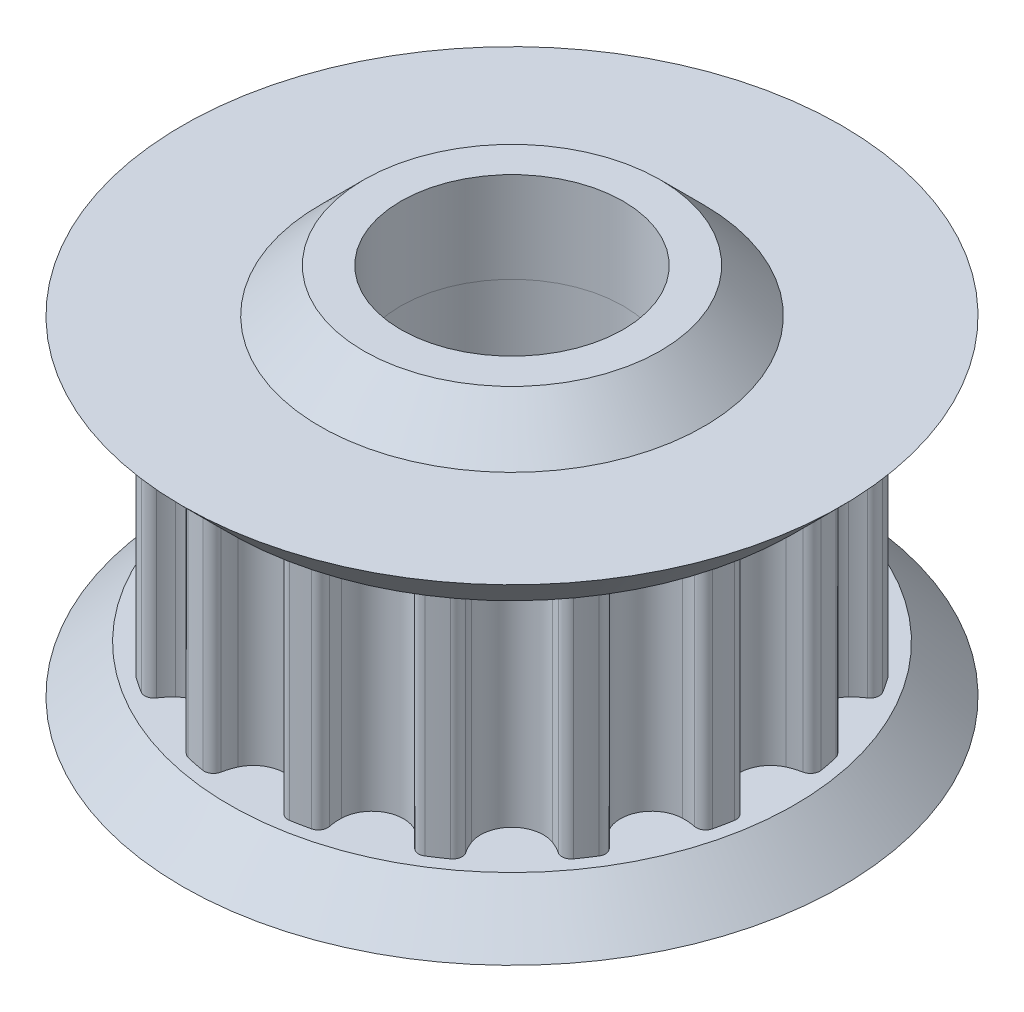
SolidWorks part; units mm, degrees
material "Alum Plate"
ref_plane "Front Plane" through (0, 0, 0) normal (0, 0, 1) x (1, 0, 0)
ref_plane "Top Plane" through (0, 0, 0) normal (0, 1, 0) x (1, 0, 0)
ref_plane "Right Plane" through (0, 0, 0) normal (1, 0, 0) x (0, 0, -1)
other "Bounding Box"
ref_plane "Default Plane" through (-8.9266, -12.7485, 0) normal (-0.1736, 0.9848, 0) x (0.9848, 0.1736, 0)
sketch "Sketch3" plane through (0, 0, 0) normal (0, 0, 1) x (1, 0, 0)
  line L0 (-7.62, 3.175) -> (-8.89, 4.445)
  line L1 (-7.62, 3.175) -> (7.62, 3.175)
  line L2 (-7.62, 3.175) -> (-7.62, -3.175)
  line L3 (-7.62, -3.175) -> (7.62, -3.175)
  line L4 (7.62, 3.175) -> (7.62, -3.175)
  line L5 (-7.62, 3.175) -> (7.62, -3.175) construction
  line L6 (-7.62, -3.175) -> (7.62, 3.175) construction
  line L7 (-8.89, 4.445) -> (-5.176, 4.445)
  line L8 (-5.176, 4.445) -> (-4, 5.621)
  line L9 (-4, 5.621) -> (0, 5.621)
  line L10 (0, 5.621) -> (0, 3.175)
  line L11 (0, -3.175) -> (0, -5.715)
  line L12 (0, -5.715) -> (-4, -5.715)
  line L13 (-4, -5.715) -> (-5.27, -4.445)
  line L14 (-5.27, -4.445) -> (-8.89, -4.445)
  line L15 (-8.89, -4.445) -> (-7.62, -3.175)
  line L16 (0, 11.4717) -> (0, 17.4749) construction
  line L17 (-3, -9.438) -> (-3, 11.1927) construction
  point P0 (0, 0)
  dimension "D1" = 6.35
  dimension "D2" = 15.24
  dimension "D3" = 45
  dimension "D4" = 45
  dimension "D5" = 11.336
  dimension "D6" = 45
  dimension "D7" = 8
  dimension "D8" = 2.54
  dimension "D9" = 1.27
  dimension "D10" = 1.27
  dimension "D11" = 3
sketch "Sketch1" plane through (0, 0, 0) normal (0, 1, 0) x (1, 0, 0)
  line L0 (0, -7.8245) -> (0, 0) construction
  circle A0 centre (0, 0) radius 3
  point P4 (-3, 0)
  point P5 (0, 0)
  arc B0 (-1.8508, -6.777) -> (-1.6633, -7.0715) centre (-1.6061, -6.8282) ccw
  arc B1 (-1.6633, -7.0715) -> (-1.1695, -7.1697) centre (0, 0) ccw
  arc B2 (-1.1695, -7.1697) -> (-0.8836, -6.9694) centre (-1.1292, -6.923) ccw
  arc B3 (-0.7739, -6.6229) -> (-0.8836, -6.9694) centre (0.61, -7.2516) ccw
  arc B4 (0.7739, -6.6229) -> (-0.7739, -6.6229) centre (0, -6.9745) ccw
  arc B5 (0.8836, -6.9694) -> (0.7739, -6.6229) centre (-0.61, -7.2516) ccw
  arc B6 (0.8836, -6.9694) -> (1.1695, -7.1697) centre (1.1292, -6.923) ccw
  arc B7 (1.1695, -7.1697) -> (1.6633, -7.0715) centre (0, 0) ccw
  arc B8 (1.6633, -7.0715) -> (1.8508, -6.777) centre (1.6061, -6.8282) ccw
  arc B9 (1.8195, -6.4149) -> (1.8508, -6.777) centre (3.3386, -6.4662) ccw
  arc B10 (3.2495, -5.8226) -> (1.8195, -6.4149) centre (2.669, -6.4436) ccw
  arc B11 (3.4834, -6.1008) -> (3.2495, -5.8226) centre (2.2115, -6.9331) ccw
  arc B12 (3.4834, -6.1008) -> (3.8242, -6.1764) centre (3.6926, -5.9639) ccw
  arc B13 (3.8242, -6.1764) -> (4.2428, -5.8967) centre (0, 0) ccw
  arc B14 (4.2428, -5.8967) -> (4.3033, -5.5529) centre (4.0968, -5.6938) ccw
  arc B15 (4.1359, -5.2303) -> (4.3033, -5.5529) centre (5.559, -4.6963) ccw
  arc B16 (5.2303, -4.1359) -> (4.1359, -5.2303) centre (4.9317, -4.9317) ccw
  arc B17 (5.5529, -4.3033) -> (5.2303, -4.1359) centre (4.6963, -5.559) ccw
  arc B18 (5.5529, -4.3033) -> (5.8967, -4.2428) centre (5.6938, -4.0968) ccw
  arc B19 (5.8967, -4.2428) -> (6.1764, -3.8242) centre (0, 0) ccw
  arc B20 (6.1764, -3.8242) -> (6.1008, -3.4834) centre (5.9639, -3.6926) ccw
  arc B21 (5.8226, -3.2495) -> (6.1008, -3.4834) centre (6.9331, -2.2115) ccw
  arc B22 (6.4149, -1.8195) -> (5.8226, -3.2495) centre (6.4436, -2.669) ccw
  arc B23 (6.777, -1.8508) -> (6.4149, -1.8195) centre (6.4662, -3.3386) ccw
  arc B24 (6.777, -1.8508) -> (7.0715, -1.6633) centre (6.8282, -1.6061) ccw
  arc B25 (7.0715, -1.6633) -> (7.1697, -1.1695) centre (0, 0) ccw
  arc B26 (7.1697, -1.1695) -> (6.9694, -0.8836) centre (6.923, -1.1292) ccw
  arc B27 (6.6229, -0.7739) -> (6.9694, -0.8836) centre (7.2516, 0.61) ccw
  arc B28 (6.6229, 0.7739) -> (6.6229, -0.7739) centre (6.9745, 0) ccw
  arc B29 (6.9694, 0.8836) -> (6.6229, 0.7739) centre (7.2516, -0.61) ccw
  arc B30 (6.9694, 0.8836) -> (7.1697, 1.1695) centre (6.923, 1.1292) ccw
  arc B31 (7.1697, 1.1695) -> (7.0715, 1.6633) centre (0, 0) ccw
  arc B32 (7.0715, 1.6633) -> (6.777, 1.8508) centre (6.8282, 1.6061) ccw
  arc B33 (6.4149, 1.8195) -> (6.777, 1.8508) centre (6.4662, 3.3386) ccw
  arc B34 (5.8226, 3.2495) -> (6.4149, 1.8195) centre (6.4436, 2.669) ccw
  arc B35 (6.1008, 3.4834) -> (5.8226, 3.2495) centre (6.9331, 2.2115) ccw
  arc B36 (6.1008, 3.4834) -> (6.1764, 3.8242) centre (5.9639, 3.6926) ccw
  arc B37 (6.1764, 3.8242) -> (5.8967, 4.2428) centre (0, 0) ccw
  arc B38 (5.8967, 4.2428) -> (5.5529, 4.3033) centre (5.6938, 4.0968) ccw
  arc B39 (5.2303, 4.1359) -> (5.5529, 4.3033) centre (4.6963, 5.559) ccw
  arc B40 (4.1359, 5.2303) -> (5.2303, 4.1359) centre (4.9317, 4.9317) ccw
  arc B41 (4.3033, 5.5529) -> (4.1359, 5.2303) centre (5.559, 4.6963) ccw
  arc B42 (4.3033, 5.5529) -> (4.2428, 5.8967) centre (4.0968, 5.6938) ccw
  arc B43 (4.2428, 5.8967) -> (3.8242, 6.1764) centre (0, 0) ccw
  arc B44 (3.8242, 6.1764) -> (3.4834, 6.1008) centre (3.6926, 5.9639) ccw
  arc B45 (3.2495, 5.8226) -> (3.4834, 6.1008) centre (2.2115, 6.9331) ccw
  arc B46 (1.8195, 6.4149) -> (3.2495, 5.8226) centre (2.669, 6.4436) ccw
  arc B47 (1.8508, 6.777) -> (1.8195, 6.4149) centre (3.3386, 6.4662) ccw
  arc B48 (1.8508, 6.777) -> (1.6633, 7.0715) centre (1.6061, 6.8282) ccw
  arc B49 (1.6633, 7.0715) -> (1.1695, 7.1697) centre (0, 0) ccw
  arc B50 (1.1695, 7.1697) -> (0.8836, 6.9694) centre (1.1292, 6.923) ccw
  arc B51 (0.7739, 6.6229) -> (0.8836, 6.9694) centre (-0.61, 7.2516) ccw
  arc B52 (-0.7739, 6.6229) -> (0.7739, 6.6229) centre (0, 6.9745) ccw
  arc B53 (-0.8836, 6.9694) -> (-0.7739, 6.6229) centre (0.61, 7.2516) ccw
  arc B54 (-0.8836, 6.9694) -> (-1.1695, 7.1697) centre (-1.1292, 6.923) ccw
  arc B55 (-1.1695, 7.1697) -> (-1.6633, 7.0715) centre (0, 0) ccw
  arc B56 (-1.6633, 7.0715) -> (-1.8508, 6.777) centre (-1.6061, 6.8282) ccw
  arc B57 (-1.8195, 6.4149) -> (-1.8508, 6.777) centre (-3.3386, 6.4662) ccw
  arc B58 (-3.2495, 5.8226) -> (-1.8195, 6.4149) centre (-2.669, 6.4436) ccw
  arc B59 (-3.4834, 6.1008) -> (-3.2495, 5.8226) centre (-2.2115, 6.9331) ccw
  arc B60 (-3.4834, 6.1008) -> (-3.8242, 6.1764) centre (-3.6926, 5.9639) ccw
  arc B61 (-3.8242, 6.1764) -> (-4.2428, 5.8967) centre (0, 0) ccw
  arc B62 (-4.2428, 5.8967) -> (-4.3033, 5.5529) centre (-4.0968, 5.6938) ccw
  arc B63 (-4.1359, 5.2303) -> (-4.3033, 5.5529) centre (-5.559, 4.6963) ccw
  arc B64 (-5.2303, 4.1359) -> (-4.1359, 5.2303) centre (-4.9317, 4.9317) ccw
  arc B65 (-5.5529, 4.3033) -> (-5.2303, 4.1359) centre (-4.6963, 5.559) ccw
  arc B66 (-5.5529, 4.3033) -> (-5.8967, 4.2428) centre (-5.6938, 4.0968) ccw
  arc B67 (-5.8967, 4.2428) -> (-6.1764, 3.8242) centre (0, 0) ccw
  arc B68 (-6.1764, 3.8242) -> (-6.1008, 3.4834) centre (-5.9639, 3.6926) ccw
  arc B69 (-5.8226, 3.2495) -> (-6.1008, 3.4834) centre (-6.9331, 2.2115) ccw
  arc B70 (-6.4149, 1.8195) -> (-5.8226, 3.2495) centre (-6.4436, 2.669) ccw
  arc B71 (-6.777, 1.8508) -> (-6.4149, 1.8195) centre (-6.4662, 3.3386) ccw
  arc B72 (-6.777, 1.8508) -> (-7.0715, 1.6633) centre (-6.8282, 1.6061) ccw
  arc B73 (-7.0715, 1.6633) -> (-7.1697, 1.1695) centre (0, 0) ccw
  arc B74 (-7.1697, 1.1695) -> (-6.9694, 0.8836) centre (-6.923, 1.1292) ccw
  arc B75 (-6.6229, 0.7739) -> (-6.9694, 0.8836) centre (-7.2516, -0.61) ccw
  arc B76 (-6.6229, -0.7739) -> (-6.6229, 0.7739) centre (-6.9745, 0) ccw
  arc B77 (-6.9694, -0.8836) -> (-6.6229, -0.7739) centre (-7.2516, 0.61) ccw
  arc B78 (-6.9694, -0.8836) -> (-7.1697, -1.1695) centre (-6.923, -1.1292) ccw
  arc B79 (-7.1697, -1.1695) -> (-7.0715, -1.6633) centre (0, 0) ccw
  arc B80 (-7.0715, -1.6633) -> (-6.777, -1.8508) centre (-6.8282, -1.6061) ccw
  arc B81 (-6.4149, -1.8195) -> (-6.777, -1.8508) centre (-6.4662, -3.3386) ccw
  arc B82 (-5.8226, -3.2495) -> (-6.4149, -1.8195) centre (-6.4436, -2.669) ccw
  arc B83 (-6.1008, -3.4834) -> (-5.8226, -3.2495) centre (-6.9331, -2.2115) ccw
  arc B84 (-6.1008, -3.4834) -> (-6.1764, -3.8242) centre (-5.9639, -3.6926) ccw
  arc B85 (-6.1764, -3.8242) -> (-5.8967, -4.2428) centre (0, 0) ccw
  arc B86 (-5.8967, -4.2428) -> (-5.5529, -4.3033) centre (-5.6938, -4.0968) ccw
  arc B87 (-5.2303, -4.1359) -> (-5.5529, -4.3033) centre (-4.6963, -5.559) ccw
  arc B88 (-4.1359, -5.2303) -> (-5.2303, -4.1359) centre (-4.9317, -4.9317) ccw
  arc B89 (-4.3033, -5.5529) -> (-4.1359, -5.2303) centre (-5.559, -4.6963) ccw
  arc B90 (-4.3033, -5.5529) -> (-4.2428, -5.8967) centre (-4.0968, -5.6938) ccw
  arc B91 (-4.2428, -5.8967) -> (-3.8242, -6.1764) centre (0, 0) ccw
  arc B92 (-3.8242, -6.1764) -> (-3.4834, -6.1008) centre (-3.6926, -5.9639) ccw
  arc B93 (-3.2495, -5.8226) -> (-3.4834, -6.1008) centre (-2.2115, -6.9331) ccw
  arc B94 (-1.8195, -6.4149) -> (-3.2495, -5.8226) centre (-2.669, -6.4436) ccw
  arc B95 (-1.8508, -6.777) -> (-1.8195, -6.4149) centre (-3.3386, -6.4662) ccw
sketch_block_instance "Block-GT2 16 Tooth Profile-1"
sketch_block "Block-GT2 16 Tooth Profile"
extrude "Boss-Extrude1" add sketch "Sketch1" along normal mid plane 6.35
sketch "Sketch4" plane through (0, 0, 0) normal (0, 0, 1) x (1, 0, 0)
  line L0 (-7.62, 3.175) -> (-3, 3.175)
  line L1 (-7.62, 3.175) -> (7.62, 3.175) construction
  line L2 (-3, 3.175) -> (-3, 5.621)
  line L3 (-4, 5.621) -> (0, 5.621) construction
  line L4 (-3, 5.621) -> (-4, 5.621)
  line L5 (-4, 5.621) -> (-5.176, 4.445)
  line L6 (-5.176, 4.445) -> (-8.89, 4.445)
  line L7 (-8.89, 4.445) -> (-7.62, 3.175)
  line L8 (-7.62, -3.175) -> (-8.89, -4.445)
  line L9 (-8.89, -4.445) -> (-5.27, -4.445)
  line L10 (-5.27, -4.445) -> (-4, -5.715)
  line L11 (-4, -5.715) -> (-3, -5.715)
  line L12 (0, -5.715) -> (-4, -5.715) construction
  line L13 (-3, -5.715) -> (-3, -3.175)
  line L14 (-7.62, -3.175) -> (7.62, -3.175) construction
  line L15 (-3, -3.175) -> (-7.62, -3.175)
  line L17 (0, 0) -> (0, 6.3277) construction
  line L21 (-3, -200009.438) -> (-3, 200011.1927) construction
  point P30 (0, 0)
  point P31 (-3, 8.89)
revolve "Revolve1" add sketch "Sketch4" angle 360 about L17
